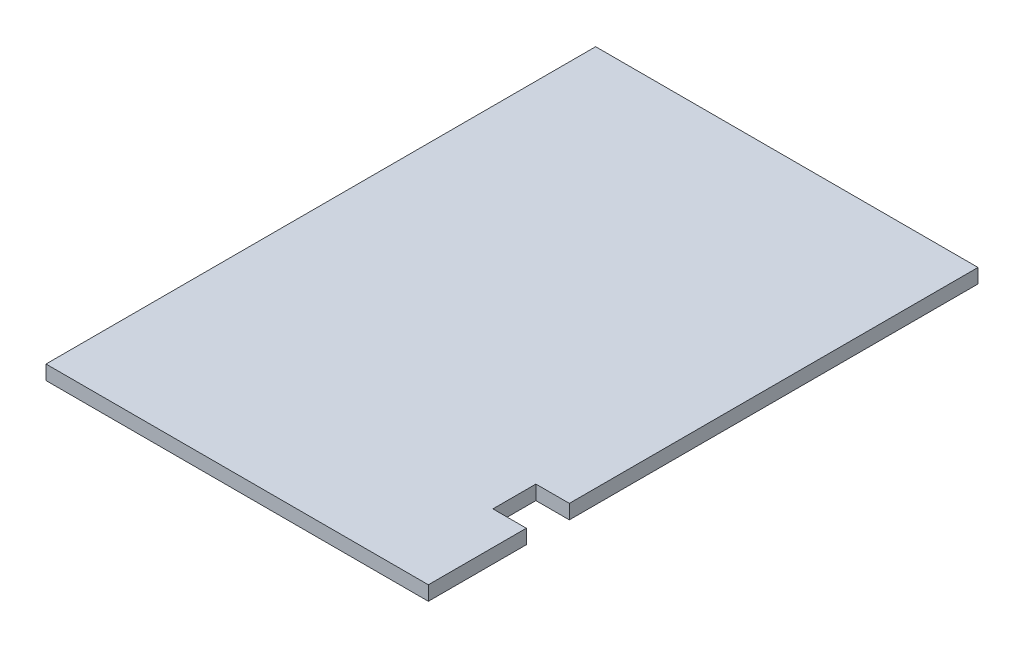
SolidWorks part; units mm, degrees
material "Acrilico TEC"
ref_plane "Front Plane" through (0, 0, 0) normal (0, 0, 1) x (1, 0, 0)
ref_plane "Top Plane" through (0, 0, 0) normal (0, 1, 0) x (1, 0, 0)
ref_plane "Right Plane" through (0, 0, 0) normal (1, 0, 0) x (0, 0, -1)
sketch "Sketch1" plane through (0, 0, 0) normal (0, 1, 0) x (1, 0, 0)
  line L1 (0, 0) -> (80, 0)
  line L2 (0, 0) -> (0, 105)
  line L3 (0, 105) -> (80, 105)
  line L4 (80, 0) -> (80, 105)
  dimension "D1" = 80
  dimension "D2" = 105
extrude "Boss-Extrude1" add sketch "Sketch1" along normal blind 3
sketch "Sketch4" plane through (0, 0, 0) normal (0, 0, 1) x (1, 0, 0)
  line L1 (0, 0) -> (80, 0)
  line L2 (0, 0) -> (0, 3)
  line L3 (0, 3) -> (80, 3)
  line L4 (80, 0) -> (80, 3)
extrude "Boss-Extrude3" add sketch "Sketch4" along normal blind 10
sketch "Sketch9" plane through (0, 3, 0) normal (0, 1, 0) x (1, 0, 0)
  line L0 (77, 15) -> (80, 15) construction
  line L1 (80, 19.5) -> (73, 19.5)
  line L2 (80, 19.5) -> (80, 10.5)
  line L3 (80, 10.5) -> (73, 10.5)
  line L4 (73, 19.5) -> (73, 10.5)
  line L5 (80, 19.5) -> (73, 10.5) construction
  line L6 (80, 10.5) -> (73, 19.5) construction
  line L8 (80, -10) -> (80, 105) construction
  dimension "D1" = 7
  dimension "D2" = 9
extrude "Cut-Extrude1" cut sketch "Sketch9" against normal blind 10
